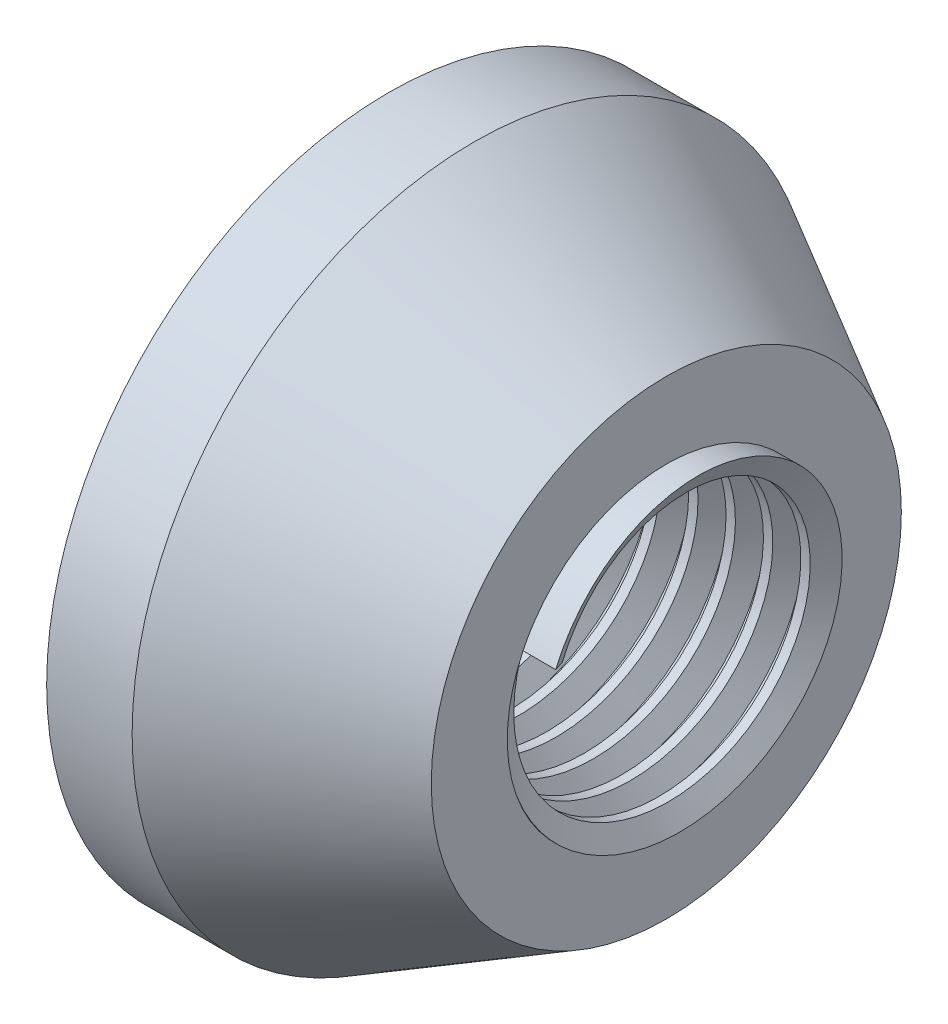
SolidWorks part; units mm, degrees
ref_plane "Front Plane" through (0, 0, 0) normal (0, 0, 1) x (1, 0, 0)
ref_plane "Top Plane" through (0, 0, 0) normal (0, 1, 0) x (1, 0, 0)
ref_plane "Right Plane" through (0, 0, 0) normal (1, 0, 0) x (0, 0, -1)
sketch "Sketch1" plane through (0, 0, 0) normal (0, 0, 1) x (1, 0, 0)
  line L0 (19.0839, 0) -> (-29.5837, 0) construction
  line L1 (-4.0972, 7.4412) -> (-4.0972, 16)
  line L2 (-4.0972, 16) -> (-0.0972, 16)
  line L3 (-0.0972, 16) -> (8.9028, 11)
  line L4 (8.9028, 11) -> (8.9028, 7.4412)
  line L5 (8.9028, 7.4412) -> (-4.0972, 7.4412)
  dimension "D1" = 16
  dimension "D2" = 11
  dimension "D3" = 13
  dimension "D4" = 9
revolve "Revolve1" add sketch "Sketch1" angle 360 about L0
thread "Thread1" pitch 1.75 method extrude profile "Thread Profile1" start angle 0, offset 0, length 0, pitch 1.75, diameter 14.8825
ref_plane "Plane1" through (-4.0972, 0, -7.4412) normal (0, -1, 0) x (0, 0, -1)
sketch "Thread Profile1" plane through (-4.0972, 0, -7.4412) normal (0, -1, 0) x (0, 0, -1)
  line L0 (0, 0) -> (0, 1.75) construction
  line L11 (0, 0) -> (0, 1.5312)
  line L12 (0, 1.5312) -> (-0.9472, 0.9844)
  line L13 (-0.9472, 0.9844) -> (-0.9472, 0.5469)
  line L15 (-0.9472, 0.5469) -> (0, 0)
  line L17 (-0.9472, 0.7656) -> (0, 0.7656) construction
  point P2 (0, 0)
  dimension "Pitch" = 1.75
  dimension "Profile_Angle" = 60
  dimension "Profile_Land" = 0.4375
  dimension "Profile_Height" = 0.9472
